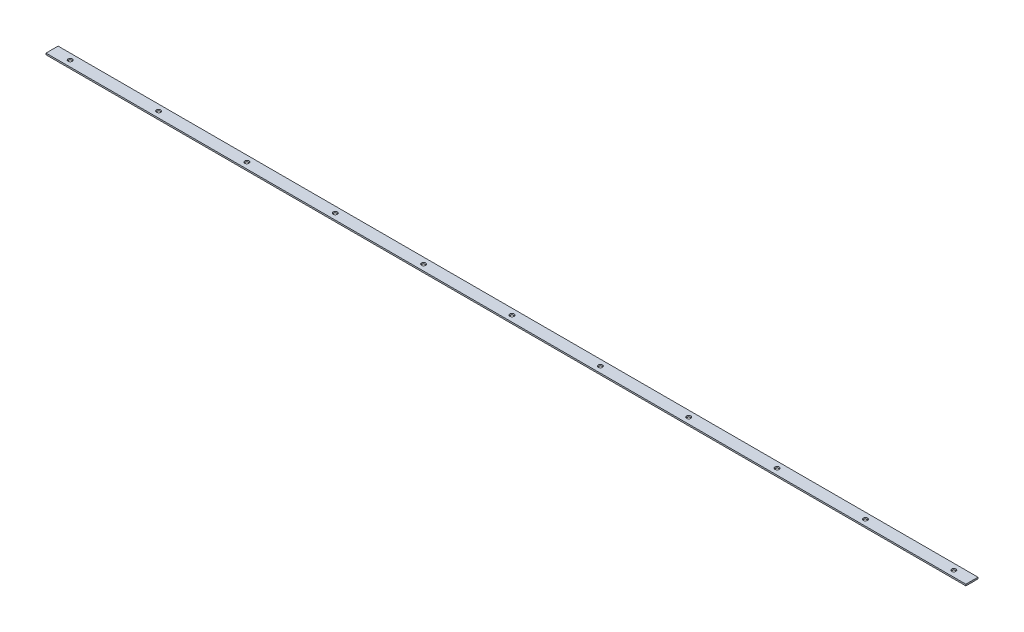
SolidWorks part; units mm, degrees
note: The reader was unsure of these and kept them because the rebuilt part matched: thickness of "Base-Flange1", "Sheet-Metal1", "Sheet-Metal2", "Sheet-Metal3".
material "AISI 304"
ref_plane "Front Plane" through (0, 0, 0) normal (0, 0, 1) x (1, 0, 0)
ref_plane "Top Plane" through (0, 0, 0) normal (0, 1, 0) x (1, 0, 0)
ref_plane "Right Plane" through (0, 0, 0) normal (1, 0, 0) x (0, 0, -1)
sketch "Sketch1" plane through (0, 0, 0) normal (0, 1, 0) x (1, 0, 0)
  line L1 (-760, -10) -> (760, -10)
  line L2 (-760, -10) -> (-760, 10)
  line L3 (-760, 10) -> (760, 10)
  line L4 (760, -10) -> (760, 10)
  line L5 (-760, -10) -> (760, 10) construction
  line L6 (-760, 10) -> (760, -10) construction
  point P0 (0, 0)
  dimension "D1" = 20
  dimension "D2" = 1520
base flange "Base-Flange1" sketch "Sketch1" thickness 2.5 reverse thickness direction no parameters "D1"=0
sketch "Sketch6" plane through (0, 0, 0) normal (0, 1, 0) x (1, 0, 0)
  circle A0 centre (0, 0) radius 3.5
  dimension "D1" = 7
extrude "Cut-Extrude1" cut sketch "Sketch6" against normal blind 10 normal cut yes
pattern_linear "LPattern1" count 6 spacing 146 along (-1, 0, 0) count 6 spacing 146 along (1, 0, 0) of "Cut-Extrude1"
sketch "Bend-Lines1" [suppressed] plane through (0, 0, 0) normal (0, 1, 0) x (1, 0, 0)
sketch "Bounding-Box1" [suppressed] plane through (0, 0, 0) normal (0, 1, 0) x (1, 0, 0)
sheet metal parameters "Sheet-Metal1" thickness 2.5 parameters "D1"=0
flat pattern "Flat-Pattern1" [suppressed]
sketch "Bend-Lines2" plane through (0, 0, 0) normal (0, 1, 0) x (1, 0, 0)
sketch3d "Bounding-Box2" [suppressed]
  line L0 (-790, 10, 0) -> (790, 10, 0) construction
  line L1 (-790, -10, 0) -> (790, -10, 0) construction
  line L2 (-790, 10, 0) -> (-790, -10, 0) construction
  line L3 (790, 10, 0) -> (790, -10, 0) construction
sheet metal parameters "Sheet-Metal2" thickness 2.5 parameters "D1"=0, "D7"=2
flat pattern "Flat-Pattern1"
sketch "Bend-Lines2" plane through (0, 0, 0) normal (0, 1, 0) x (1, 0, 0)
sketch3d "Bounding-Box2" [suppressed]
  line L0 (790, 10, 0) -> (-790, 10, 0) construction
  line L1 (790, -10, 0) -> (-790, -10, 0) construction
  line L2 (790, 10, 0) -> (790, -10, 0) construction
  line L3 (-790, 10, 0) -> (-790, -10, 0) construction
sheet metal parameters "Sheet-Metal3" thickness 2.5 parameters "D1"=0, "D7"=2
flat pattern "Flat-Pattern1"
sketch "Bend-Lines2" plane through (0, 0, 0) normal (0, 1, 0) x (1, 0, 0)
sketch3d "Bounding-Box2" [suppressed]
  line L0 (760, 10, 0) -> (-760, 10, 0) construction
  line L1 (760, -10, 0) -> (-760, -10, 0) construction
  line L2 (760, 10, 0) -> (760, -10, 0) construction
  line L3 (-760, 10, 0) -> (-760, -10, 0) construction
